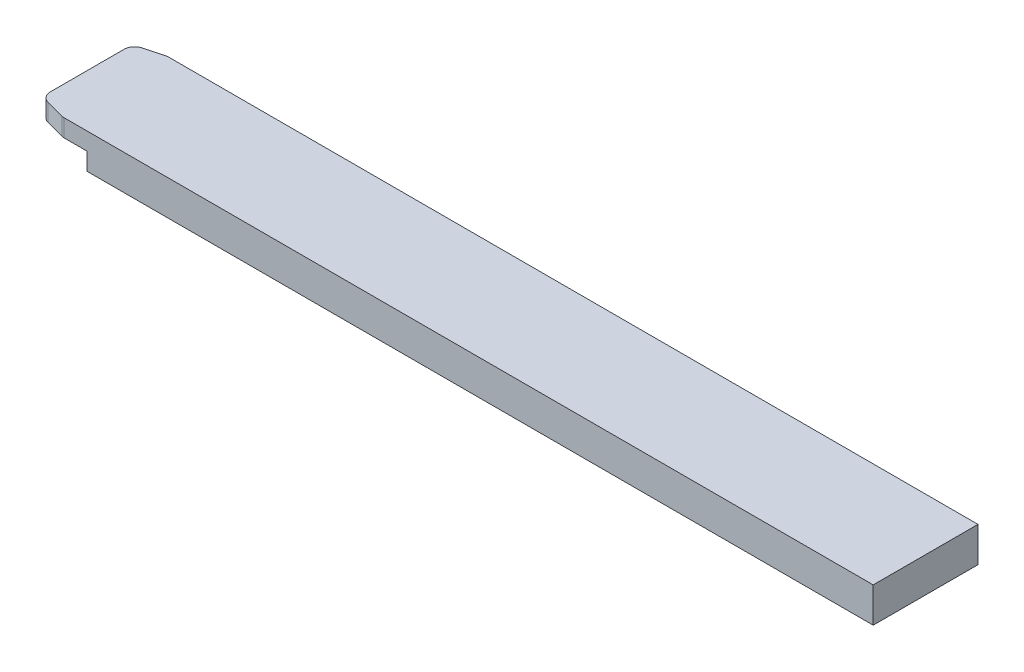
SolidWorks part; units mm, degrees
material "3.1355 (EN-AW 2024)"
ref_plane "Front" through (0, 0, 0) normal (0, 0, 1) x (1, 0, 0)
ref_plane "Top" through (0, 0, 0) normal (0, 1, 0) x (1, 0, 0)
ref_plane "Right" through (0, 0, 0) normal (1, 0, 0) x (0, 0, -1)
sketch "Эскиз1" plane through (0, 0, 0) normal (0, 1, 0) x (1, 0, 0)
  line L0 (240, 15) -> (15, 15) construction
  line L1 (15, 0) -> (240, 0)
  line L2 (0, 0) -> (0, 30) construction
  line L3 (15, 30) -> (240, 30)
  line L4 (240, 0) -> (240, 30)
  line L5 (0, 0) -> (15, 0) construction
  line L6 (0, 2.1436) -> (0, 27.8564)
  line L7 (15, 30) -> (8, 30)
  line L8 (8, 30) -> (0, 27.8564)
  line L9 (8, 0) -> (0, 2.1436)
  line L10 (15, 0) -> (8, 0)
  arc A0 (15, 30) -> (15, 0) centre (15, 15) ccw construction
  point P13 (0, 15)
  dimension "D1" = 30
  dimension "D2" = 240
  dimension "D4" = 7
  dimension "D5" = 75
extrude "Бобышка-Вытянуть1" add sketch "Эскиз1" along normal blind 10
sketch "Эскиз4" plane through (0, 0, 0) normal (0, -1, 0) x (1, 0, 0)
  line L0 (8, 0) -> (240, 0) construction
  line L1 (0, -30) -> (15, -30)
  line L2 (0, -30) -> (0, 0)
  line L3 (0, 0) -> (15, 0)
  line L4 (15, -30) -> (15, 0)
  line L5 (0, -27.8564) -> (0, -2.1436) construction
  line L6 (240, -30) -> (8, -30) construction
  dimension "D1" = 15
extrude "Вырез-Вытянуть2" cut sketch "Эскиз4" against normal blind 5
fillet "Скругление1" radius 3 4 edges at (8, 7.5, -30) (0, 7.5, -27.8564) (0, 7.5, -2.1436) (8, 7.5, 0)
